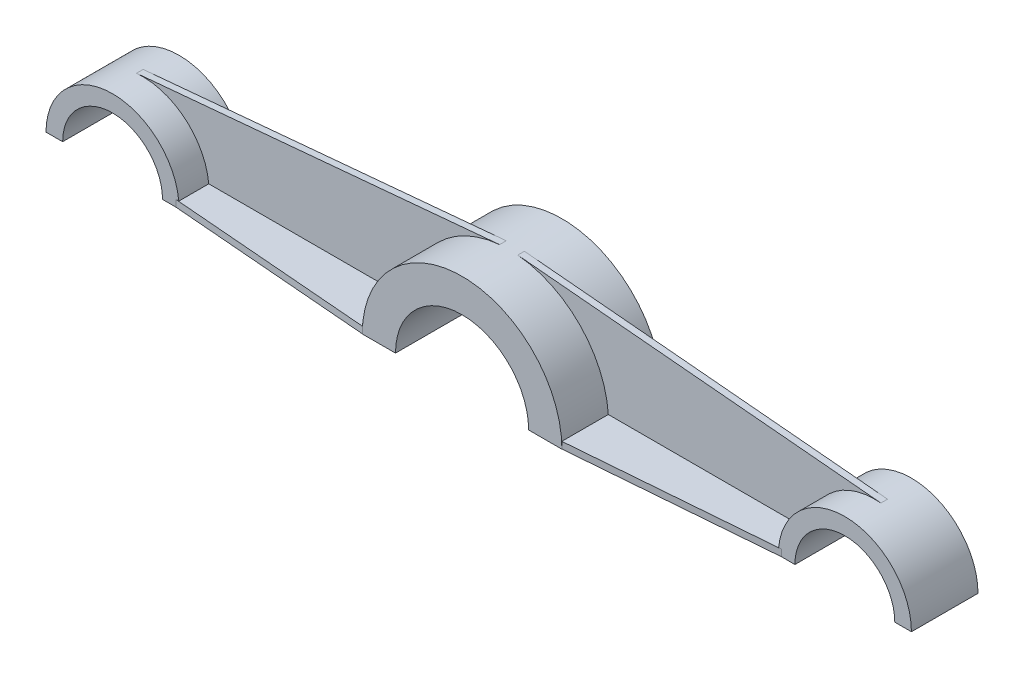
SolidWorks part; units mm, degrees
ref_plane "Front Plane" through (0, 0, 0) normal (0, 0, 1) x (1, 0, 0)
ref_plane "Top Plane" through (0, 0, 0) normal (0, 1, 0) x (1, 0, 0)
ref_plane "Right Plane" through (0, 0, 0) normal (1, 0, 0) x (0, 0, -1)
sketch "Sketch1" plane through (0, 0, 0) normal (0, 0, 1) x (1, 0, 0)
  line L0 (-186.2894, 0) -> (148.6656, 0) construction
  line L1 (-130, 0) -> (-125, 0)
  line L2 (-95, 0) -> (-90, 0)
  line L3 (-30, 0) -> (-20, 0)
  line L4 (20, 0) -> (30, 0)
  line L5 (90, 0) -> (95, 0)
  line L6 (125, 0) -> (130, 0)
  arc A0 (30, 0) -> (-30, 0) centre (0, 0) ccw
  arc A1 (20, 0) -> (-20, 0) centre (0, 0) ccw
  arc A2 (130, 0) -> (90, 0) centre (110, 0) ccw
  arc A3 (125, 0) -> (95, 0) centre (110, 0) ccw
  arc A4 (-90, 0) -> (-130, 0) centre (-110, 0) ccw
  arc A5 (-95, 0) -> (-125, 0) centre (-110, 0) ccw
  dimension "D1" = 60
  dimension "D2" = 40
  dimension "D3" = 40
  dimension "D4" = 30
  dimension "D5" = 110
  dimension "D6" = 220
extrude "Boss-Extrude1" add sketch "Sketch1" along normal mid plane 30 contours A0 L3 A1 L4
extrude "Boss-Extrude2" add sketch "Sketch1<3>" along normal mid plane 20 separate body contours A4 L1 A5 L2 | A2 L5 A3 L6
sketch "Sketch1<3>" plane through (0, 0, 0) normal (0, 0, 1) x (1, 0, 0) same geometry as "Sketch1"
sketch "Sketch2" plane through (0, 0, 0) normal (0, 0, 1) x (1, 0, 0)
  line L0 (-111.8182, 19.9172) -> (-2.7273, 29.8758)
  line L1 (2.7273, 29.8758) -> (111.8182, 19.9172)
  line L2 (-90, 0) -> (-30, 0)
  line L3 (30, 0) -> (90, 0)
  arc A0 (130, 0) -> (90, 0) centre (110, 0) ccw construction
  arc A1 (30, 0) -> (-30, 0) centre (0, 0) ccw construction
  arc A2 (-90, 0) -> (-130, 0) centre (-110, 0) ccw construction
  arc A3 (111.8182, 19.9172) -> (90, 0) centre (110, 0) ccw
  arc A4 (30, 0) -> (2.7273, 29.8758) centre (0, 0) ccw
  arc A5 (-90, 0) -> (-111.8182, 19.9172) centre (-110, 0) ccw
  arc A6 (-2.7273, 29.8758) -> (-30, 0) centre (0, 0) ccw
extrude "Boss-Extrude3" add sketch "Sketch2" along normal mid plane 2
sketch "Sketch3" plane through (0, 0, 0) normal (0, 1, 0) x (1, 0, 0)
  line L0 (-30, -15) -> (30, -15) construction
  line L2 (-130, -10) -> (-130, 10) construction
  line L3 (91, 10) -> (91, -10)
  line L4 (-29.5, 15) -> (-29.5, -15)
  line L5 (130, -10) -> (130, 10) construction
  line L6 (-91, 10) -> (-29.5, 15)
  line L7 (29.5, 15) -> (91, 10)
  line L8 (-16.5, 0) -> (16.5, 0) construction
  line L9 (-90, 10) -> (-130, 10) construction
  line L10 (29.5, -15) -> (91, -10)
  line L11 (90, -10) -> (130, -10) construction
  line L12 (-91, -10) -> (-29.5, -15)
  line L14 (-91, 10) -> (-91, -10)
  line L15 (29.5, 15) -> (29.5, -15)
  point P0 (28.7928, -15)
  dimension "D1" = 29.5
  dimension "D2" = 29.5
  dimension "D3" = 39
  dimension "D4" = 39
extrude "Boss-Extrude8" add sketch "Sketch3" along normal blind 2
